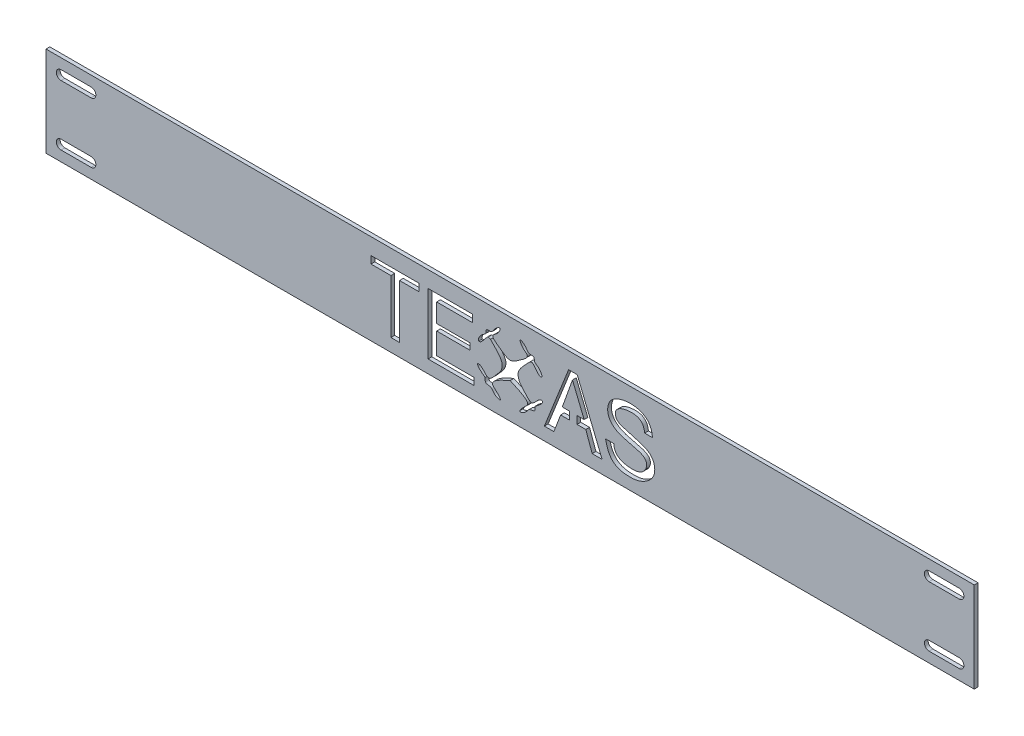
SolidWorks part; units mm, degrees
material "ABS"
ref_plane "Front Plane" through (0, 0, 0) normal (0, 0, 1) x (1, 0, 0)
ref_plane "Top Plane" through (0, 0, 0) normal (0, 1, 0) x (1, 0, 0)
ref_plane "Right Plane" through (0, 0, 0) normal (1, 0, 0) x (0, 0, -1)
sketch "Sketch1" plane through (0, 0, 0) normal (0, 1, 0) x (1, 0, 0)
  line L0 (0, 0) -> (391.795, 0)
  line L1 (391.795, 0) -> (391.795, 1.5875)
  line L2 (391.795, 1.5875) -> (366.395, 1.5875)
  line L5 (0, 0) -> (0, 1.5875)
  line L6 (0, 1.5875) -> (25.4, 1.5875)
  line L8 (25.4, 1.5875) -> (366.395, 1.5875)
  dimension "D1" = 391.795
  dimension "D2" = 25.4
  dimension "D3" = 1.5875
  dimension "D5" = 1.5875
  dimension "D6" = 25.4
extrude "Boss-Extrude1" add sketch "Sketch1" along normal blind 38.1
sketch "Sketch2" plane through (0, 0, 0) normal (0, 0, 1) x (1, 0, 0)
  line L0 (195.8975, 38.1) -> (195.8975, 0) construction
  line L1 (0, 38.1) -> (391.795, 38.1) construction
  line L2 (0, 0) -> (391.795, 0) construction
  line L3 (283.313, 163.9097) -> (903.9797, 163.9097) construction
  line L4 (145.5995, 5.4278) -> (149.2255, 5.4278)
  line L5 (149.2255, 5.4278) -> (149.2255, 28.0908)
  line L6 (149.2255, 28.0908) -> (157.5137, 28.0908)
  line L7 (157.5137, 28.0908) -> (157.5137, 31.1989)
  line L8 (157.5137, 31.1989) -> (137.1818, 31.1989)
  line L9 (137.1818, 31.1989) -> (137.1818, 28.0908)
  line L10 (137.1818, 28.0908) -> (145.5995, 28.0908)
  line L11 (145.5995, 28.0908) -> (145.5995, 5.4278)
  line L12 (161.2693, 31.1989) -> (161.2693, 5.4278)
  line L13 (161.2693, 5.4278) -> (180.6947, 5.4278)
  line L14 (180.6947, 5.4278) -> (180.6947, 8.4064)
  line L15 (180.6947, 8.4064) -> (164.8954, 8.4064)
  line L16 (164.8954, 8.4064) -> (164.8954, 17.4716)
  line L17 (164.8954, 17.4716) -> (179.0112, 17.4716)
  line L18 (179.0112, 17.4716) -> (179.0112, 20.1911)
  line L19 (179.0112, 20.1911) -> (164.8954, 20.1911)
  line L20 (164.8954, 20.1911) -> (164.8954, 28.0908)
  line L21 (164.8954, 28.0908) -> (179.9177, 28.0908)
  line L22 (179.9177, 28.0908) -> (179.9177, 31.1989)
  line L23 (179.9177, 31.1989) -> (161.2693, 31.1989)
  line L24 (210.3508, 5.4278) -> (214.3654, 5.4278)
  line L25 (214.3654, 5.4278) -> (217.2144, 12.939)
  line L26 (217.2144, 12.939) -> (221.0483, 12.939)
  line L27 (227.8337, 12.939) -> (230.539, 5.4669)
  line L28 (230.539, 5.4669) -> (234.7081, 5.4669)
  line L29 (234.7081, 5.4669) -> (224.208, 31.1824)
  line L30 (224.208, 31.1824) -> (220.575, 31.1824)
  line L31 (220.575, 31.1824) -> (210.3508, 5.4278)
  line L32 (236.1849, 13.6984) -> (239.6466, 13.6984)
  line L33 (239.6466, 13.6984) -> (239.7923, 13.5158)
  line L34 (252.6939, 24.0431) -> (255.9649, 24.0431)
  line L35 (217.9175, 16.2101) -> (221.0483, 16.2101)
  line L36 (227.1281, 16.2101) -> (222.2126, 28.2483)
  line L37 (221.0483, 16.2101) -> (221.0483, 12.939)
  line L38 (217.9175, 16.2101) -> (222.2126, 28.2483)
  line L39 (224.1108, 12.939) -> (224.1108, 16.2101)
  line L40 (224.1108, 16.2101) -> (227.1281, 16.2101)
  line L41 (224.1108, 12.939) -> (227.8337, 12.939)
  spline S0 degree 3 poles (236.1849, 13.6984) (237.5399, 6.2857) (242.061, 4.7896) (251.5619, 4.9591) (257.3774, 9.0424) (256.4748, 18.5272) (250.9642, 19.3892) (242.9519, 21.83) (240.4122, 22.5977) (240.1126, 27.5392) (247.0684, 29.749) (252.2417, 27.9482) (252.6939, 24.0431) knots 0 0 0 0 0.215234 0.260043 0.427196 0.476118 0.700347 0.738892 0.823025 0.844326 0.930603 1 1 1 1
  spline S1 degree 3 poles (255.9649, 24.0431) (255.7758, 27.851) (251.0898, 33.4535) (238.7878, 31.3657) (236.3033, 23.767) (238.3883, 19.2346) (248.3318, 16.6064) (253.26, 15.8673) (253.7071, 11.2879) (251.4462, 8.1621) (244.1527, 8.2706) (239.8501, 9.5417) (239.6466, 13.6984) knots 0 0 0 0 0.15898 0.386457 0.435551 0.626101 0.666569 0.799769 0.826978 0.911452 0.92981 1 1 1 1
  spline S2 degree 3 poles (185.3714, 10.7296) (182.8407, 12.4351) (181.6655, 14.1401) (183.6751, 14.5574) (184.9275, 12.4615) (186.8292, 11.0476) (187.45, 11.2677) (188.6725, 12.4902) knots 0 0 0 0 0.181966 0.253331 0.662504 0.742285 1 1 1 1
  spline S3 degree 3 poles (188.6725, 12.4902) (190.7341, 14.6912) (192.1741, 16.0846) (192.9468, 20.7187) (190.0982, 23.1306) (187.6077, 25.8015) knots 0 0 0 0 0.394262 0.494262 1 1 1 1
  spline S4 degree 3 poles (187.6077, 25.8015) (186.8624, 26.2618) (185.6011, 25.8447) (183.7435, 22.2335) (182.6564, 22.6806) knots 0 0 0 0 0.315304 1 1 1 1
  spline S5 degree 3 poles (182.6564, 22.6806) (182.1354, 23.0491) (183.4336, 25.626) (184.7536, 26.1029) (185.8486, 27.0652) (185.3705, 29.0689) (188.4505, 28.1985) (188.9787, 30.6833) (192.7623, 32.8587) (190.4864, 28.8936) (188.5646, 28.1107) (188.731, 26.5406) (192.1892, 24.0631) (194.829, 22.225) (195.8975, 22.3083) knots 0 0 0 0 0.138762 0.259763 0.279833 0.339467 0.421315 0.521202 0.623024 0.751654 0.836143 0.853089 0.921123 1 1 1 1
  spline S6 degree 3 poles (185.3714, 10.7296) (185.246, 9.0028) (185.9848, 8.6457) (188.2535, 8.5895) (188.9192, 6.321) (192.9454, 4.9101) (190.179, 8.1591) (186.0227, 11.1248) (195.1228, 14.3553) (195.8975, 14.8584) knots 0 0 0 0 0.059561 0.13238 0.259094 0.360158 0.491405 0.59516 1 1 1 1
  spline S7 degree 3 poles (206.4236, 10.7296) (206.549, 9.0028) (205.8102, 8.6457) (203.5415, 8.5895) (202.8758, 6.321) (198.8496, 4.9101) (201.616, 8.1591) (205.7723, 11.1248) (196.6722, 14.3553) (195.8975, 14.8584) knots 0 0 0 0 0.059561 0.13238 0.259094 0.360158 0.491405 0.59516 1 1 1 1
  spline S8 degree 3 poles (206.4236, 10.7296) (208.9543, 12.4351) (210.1295, 14.1401) (208.1199, 14.5574) (206.8675, 12.4615) (204.9658, 11.0476) (204.345, 11.2677) (203.1225, 12.4902) knots 0 0 0 0 0.181966 0.253331 0.662504 0.742285 1 1 1 1
  spline S9 degree 3 poles (203.1225, 12.4902) (201.0609, 14.6912) (199.6209, 16.0846) (198.8482, 20.7187) (201.6968, 23.1306) (204.1873, 25.8015) knots 0 0 0 0 0.394262 0.494262 1 1 1 1
  spline S10 degree 3 poles (204.1873, 25.8015) (204.9326, 26.2618) (206.1939, 25.8447) (208.0515, 22.2335) (209.1386, 22.6806) knots 0 0 0 0 0.315304 1 1 1 1
  spline S11 degree 3 poles (209.1386, 22.6806) (209.6596, 23.0491) (208.3614, 25.626) (207.0414, 26.1029) (205.9464, 27.0652) (206.4245, 29.0689) (203.3445, 28.1985) (202.8163, 30.6833) (199.0327, 32.8587) (201.3086, 28.8936) (203.2304, 28.1107) (203.064, 26.5406) (199.6058, 24.0631) (196.966, 22.225) (195.8975, 22.3083) knots 0 0 0 0 0.138762 0.259763 0.279833 0.339467 0.421315 0.521202 0.623024 0.751654 0.836143 0.853089 0.921123 1 1 1 1
extrude "Cut-Extrude1" cut sketch "Sketch2" against normal through all contours L10 L11 L4 L5 L6 L7 L8 L9 | L22 L23 L12 L13 L14 L15 L16 L17 L18 L19 L20 L21 | S10 S11 S5 S4 S3 S2 S6 S7 S8 S9 | L30 L31 L24 L25 L26 L27 L28 L29 | L34 S1 L32 S0 | L30 region at (147.3844, 22.3607, 0) region at (168.5479, 18.3695, 0) region at (215.7923, 18.1743, 0) region at (246.6536, 18.1031, 0) region at (195.8975, 18.6027, 0)
sketch "Sketch3" plane through (0, 0, 0) normal (0, 0, 1) x (1, 0, 0)
  line L0 (195.8975, 38.1) -> (195.8975, 0) construction
  line L1 (0, 38.1) -> (391.795, 38.1) construction
  line L2 (0, 0) -> (391.795, 0) construction
  line L3 (195.8975, 19.05) -> (0, 19.05) construction
  line L4 (0, 38.1) -> (0, 0) construction
  line L5 (6.35, 31.75) -> (19.05, 31.75) construction
  line L6 (6.35, 33.7344) -> (19.05, 33.7344)
  line L7 (6.35, 29.7656) -> (19.05, 29.7656)
  line L8 (6.35, 6.35) -> (19.05, 6.35) construction
  line L9 (6.35, 4.3656) -> (19.05, 4.3656)
  line L10 (6.35, 8.3344) -> (19.05, 8.3344)
  line L11 (385.445, 6.35) -> (372.745, 6.35) construction
  line L12 (385.445, 4.3656) -> (372.745, 4.3656)
  line L13 (385.445, 8.3344) -> (372.745, 8.3344)
  line L14 (385.445, 31.75) -> (372.745, 31.75) construction
  line L15 (385.445, 33.7344) -> (372.745, 33.7344)
  line L16 (385.445, 29.7656) -> (372.745, 29.7656)
  arc A0 (6.35, 33.7344) -> (6.35, 29.7656) centre (6.35, 31.75) ccw
  arc A1 (19.05, 29.7656) -> (19.05, 33.7344) centre (19.05, 31.75) ccw
  arc A2 (6.35, 4.3656) -> (6.35, 8.3344) centre (6.35, 6.35) cw
  arc A3 (19.05, 8.3344) -> (19.05, 4.3656) centre (19.05, 6.35) cw
  arc A4 (385.445, 4.3656) -> (385.445, 8.3344) centre (385.445, 6.35) ccw
  arc A5 (372.745, 8.3344) -> (372.745, 4.3656) centre (372.745, 6.35) ccw
  arc A6 (385.445, 33.7344) -> (385.445, 29.7656) centre (385.445, 31.75) cw
  arc A7 (372.745, 29.7656) -> (372.745, 33.7344) centre (372.745, 31.75) cw
  point P12 (12.7, 31.75)
  point P19 (12.7, 6.35)
  point P26 (379.095, 6.35)
  point P33 (379.095, 31.75)
  dimension "D1" = 12.7
  dimension "D2" = 3.9688
  dimension "D3" = 12.7
  dimension "D4" = 6.35
extrude "Cut-Extrude2" cut sketch "Sketch3" against normal through all
